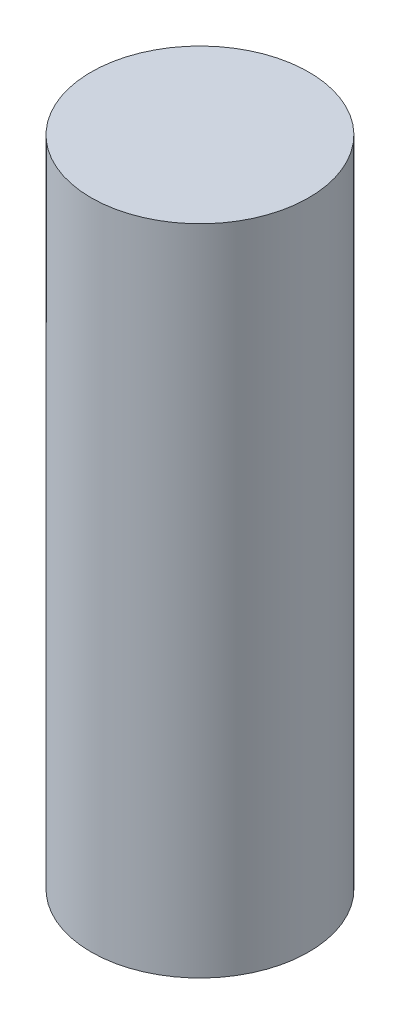
SolidWorks part; units mm, degrees
material "Silicon"
ref_plane "Front Plane" through (0, 0, 0) normal (0, 0, 1) x (1, 0, 0)
ref_plane "Top Plane" through (0, 0, 0) normal (0, 1, 0) x (1, 0, 0)
ref_plane "Right Plane" through (0, 0, 0) normal (1, 0, 0) x (0, 0, -1)
sketch "Main Parachute Bag Profile" plane through (0, 0, 0) normal (0, 1, 0) x (1, 0, 0)
  circle A0 centre (0, 0) radius 63.5
  dimension "D1" = 127
extrude "Main Parachute Bag Body" add sketch "Main Parachute Bag Profile" along normal blind 381 contours A0
equation "\"Packed Length\"= 15"
equation "\"Packed Diameter\"= 5"
equation "\"D1@Main Parachute Bag Body\"=\"Packed Length\""
